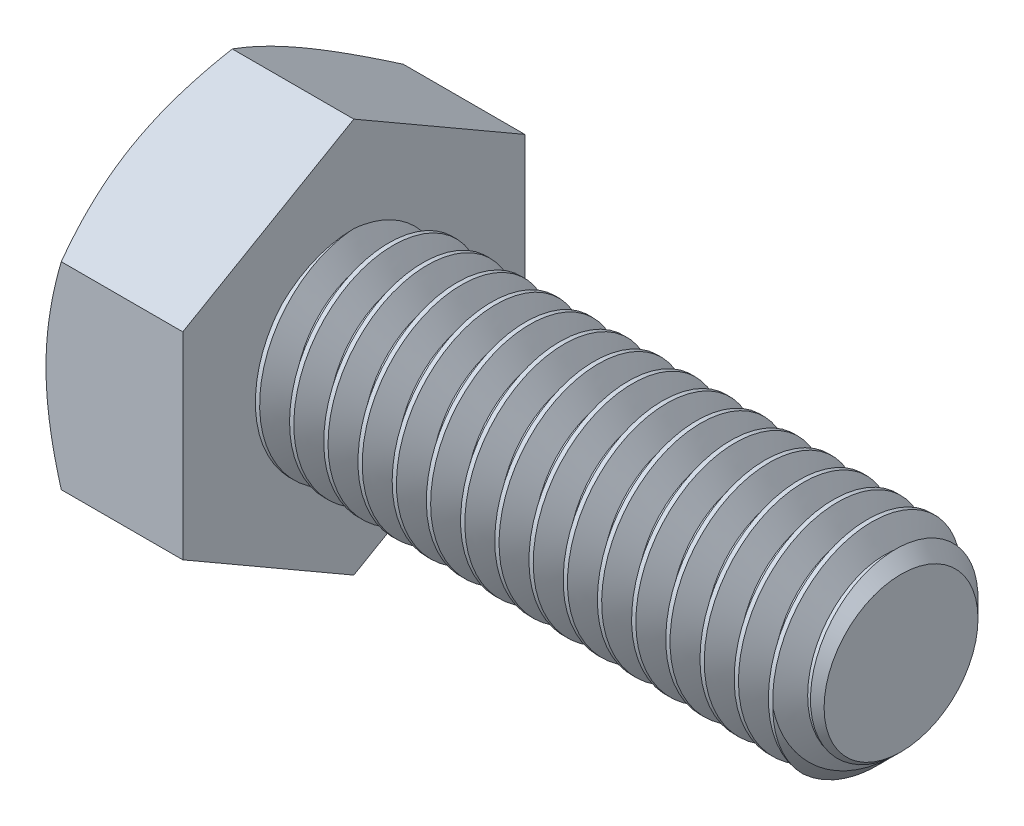
SolidWorks part; units mm, degrees
ref_plane "Front Plane" through (0, 0, 0) normal (0, 0, 1) x (1, 0, 0)
ref_plane "Top Plane" through (0, 0, 0) normal (0, 1, 0) x (1, 0, 0)
ref_plane "Right Plane" through (0, 0, 0) normal (1, 0, 0) x (0, 0, -1)
sketch "Sketch1" plane through (0, 0, 0) normal (0, 0, 1) x (1, 0, 0)
  line L0 (-10, 0) -> (10, 0) construction
  line L1 (-6, 5) -> (-6, -5) construction
  line L2 (-10, 5) -> (-10, -5) construction
  line L3 (10, 3) -> (10, -3) construction
  point P8 (6.5, -3)
  dimension "Thread Dia" = 6
  dimension "Hex" = 10
  dimension "Head Ht" = 4
  dimension "Length" = 16
  dimension "D1" = 3.5
ref_plane "Plane2" through (10, 0, 0) normal (1, 0, 0) x (0, 0, -1)
sketch "Sketch2" plane through (10, 0, 0) normal (1, 0, 0) x (0, 0, -1)
  circle A0 centre (0, 0) radius 3
extrude "Boss-Extrude1" add sketch "Sketch2" against normal up to vertex (16 mm away) up to point (-6, -5, 0)
sketch "Sketch4" plane through (10, 0, 0) normal (1, 0, 0) x (0, 0, -1)
  circle A1 centre (0, 0) radius 3
  circle A2 centre (0, 0) radius 3
  dimension "D1" = 0
curve "Helix/Spiral1" pitch 1 height 17 turns 17 parameters "Pitch"=1
chamfer "Chamfer1" distance 0.75 angle 45 1 edges at (10, 0, -3)
sketch "Sketch5" plane through (0, 0, 0) normal (0, 0, 1) x (1, 0, 0)
  line L0 (10, 3) -> (10.375, 2.3505)
  line L1 (10.375, 2.3505) -> (10.5, 2.3505)
  line L2 (10.5, 2.3505) -> (10.875, 3)
  line L3 (10, 3) -> (10.875, 3)
  line L4 (10.4375, 2.3505) -> (10.4375, 3) construction
  line L5 (10.1875, 2.6752) -> (10.6875, 2.6752) construction
  line L6 (10, -3) -> (10, 3) construction
  dimension "D1" = 60
  dimension "D2" = 0.125
  dimension "D3" = 0.5
sweep "Cut-Sweep1" cut profiles "Sketch5" path "Helix/Spiral1"
sketch "Sketch3" plane through (-6, 0, 0) normal (-1, 0, 0) x (0, 0, 1)
  line L0 (0, 5) -> (0, -5) construction
  line L1 (-5, -2.8868) -> (0, -5.7735)
  line L2 (0, -5.7735) -> (5, -2.8868)
  line L3 (5, -2.8868) -> (5, 2.8868)
  line L4 (5, 2.8868) -> (0, 5.7735)
  line L5 (0, 5.7735) -> (-5, 2.8868)
  line L6 (-5, 2.8868) -> (-5, -2.8868)
  circle A0 centre (0, 0) radius 5 construction
extrude "Boss-Extrude2" add sketch "Sketch3" along normal up to vertex (4 mm away) up to point (-10, -5, 0)
sketch "Sketch6" plane through (-10, 0, 0) normal (-1, 0, 0) x (0, 0, 1)
  circle A0 centre (0, 0) radius 5 construction
  circle A1 centre (0, 0) radius 5
extrude "Cut-Extrude1" cut sketch "Sketch6" against normal through all draft 60 flip side to cut
sketch "Sketch7" plane through (-10, 0, 0) normal (-1, 0, 0) x (0, 0, 1)
  line L0 (0, 0) -> (0, 5) construction
  line L2 (0, 5) -> (0, -5) construction
  line L3 (-4.3301, 2.5) -> (4.3301, 2.5) construction
  circle A1 centre (0, 0) radius 5 construction
  text T0 "10.9\r\n" font "Arial" height in points 6
  point P8 (0, 2.5)
extrude "Cut-Extrude2" cut sketch "Sketch7" against normal blind 0.5
equation "\"D2@Sketch5\" = \"Pitch@Helix/Spiral1\"*.125"
equation "\"D3@Sketch5\" = \"Pitch@Helix/Spiral1\"*.50"
equation "\"D3@Helix/Spiral1\" = \"Length@Sketch1\"+\"Pitch@Helix/Spiral1\""
equation "\"D1@Chamfer1\" = \"Pitch@Helix/Spiral1\"*.750"
equation "\"D1@Sketch1\" = \"Pitch@Helix/Spiral1\"*3.50"
